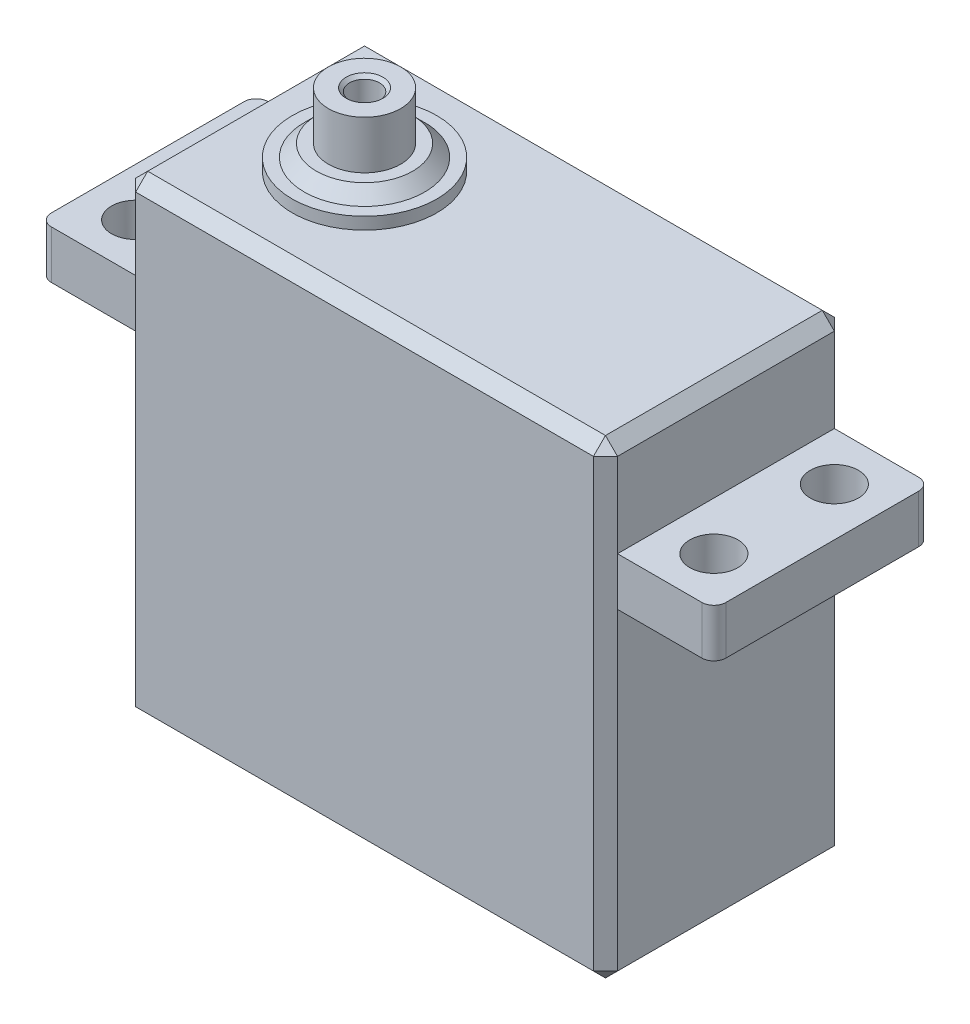
SolidWorks part; units mm, degrees
ref_plane "前视基准面" through (0, 0, 0) normal (0, 0, 1) x (1, 0, 0)
ref_plane "上视基准面" through (0, 0, 0) normal (0, 1, 0) x (1, 0, 0)
ref_plane "右视基准面" through (0, 0, 0) normal (1, 0, 0) x (0, 0, -1)
other "Configuration Table"
sketch "草图1" plane through (0, 0, 0) normal (0, 1, 0) x (1, 0, 0)
  line L1 (-20, -10) -> (20, -10)
  line L2 (-20, -10) -> (-20, 10)
  line L3 (-20, 10) -> (20, 10)
  line L4 (20, -10) -> (20, 10)
  line L5 (-20, -10) -> (20, 10) construction
  line L6 (-20, 10) -> (20, -10) construction
  point P0 (0, 0)
  dimension "D1" = 20
  dimension "D2" = 40
extrude "凸台-拉伸1" add sketch "草图1" along normal blind 39
chamfer "倒角1" distance 1 angle 45 12 edges at (20, 0, 0) (0, 0, -10) (-20, 0, 0) (0, 0, 10) (20, 39, 0) (20, 19.5, -10) (0, 39, -10) (20, 19.5, 10) (0, 39, 10) (-20, 19.5, 10) (-20, 39, 0) (-20, 19.5, -10)
sketch "草图12" plane through (-20, 0, 0) normal (-1, 0, 0) x (0, 0, 1)
  line L0 (9, 1) -> (9, 38) construction
  line L1 (-9, 27) -> (9, 27)
  line L2 (-9, 27) -> (-9, 31)
  line L3 (-9, 31) -> (9, 31)
  line L4 (9, 27) -> (9, 31)
  line L5 (-9, 27) -> (9, 31) construction
  line L6 (-9, 31) -> (9, 27) construction
  line L8 (9, 0) -> (-9, 0) construction
  line L9 (-9, 38) -> (-9, 1) construction
  point P0 (0, 29)
  dimension "D1" = 31
  dimension "D2" = 4
extrude "凸台-拉伸7" add sketch "草图12" along normal blind 8
mirror "镜向1" about plane through (0, 0, 0) normal (1, 0, 0) of "凸台-拉伸7"
sketch "草图13" plane through (0, 31, 0) normal (0, 1, 0) x (1, 0, 0)
  line L0 (-32.0979, 0) -> (34.7095, 0) construction
  line L1 (0, 14.3851) -> (0, -15.5224) construction
  circle A0 centre (-24, 5) radius 2
  circle A1 centre (-24, -5) radius 2
  circle A2 centre (24, -5) radius 2
  circle A3 centre (24, 5) radius 2
  dimension "D2" = 4
  dimension "D1" = 10
  dimension "D3" = 48
extrude "切除-拉伸2" cut sketch "草图13" against normal through all
fillet "圆角3" radius 1 4 edges at (28, 29, -9) (28, 29, 9) (-28, 29, 9) (-28, 29, -9)
sketch "草图14" plane through (0, 39, 0) normal (0, 1, 0) x (1, 0, 0)
  line L0 (-26.5797, 0) -> (3.9596, 0) construction
  circle A0 centre (-24, 5) radius 2 construction
  circle A1 centre (-24, 5) radius 2 construction
  circle A2 centre (-10, 0) radius 6
  dimension "D1" = 12
  dimension "D2" = 14
extrude "凸台-拉伸8" add sketch "草图14" along normal blind 1
sketch "草图15" plane through (0, 40, 0) normal (0, 1, 0) x (1, 0, 0)
  circle A0 centre (-10, 0) radius 5
  dimension "D1" = 10
extrude "凸台-拉伸9" add sketch "草图15" along normal blind 1
sketch "草图16" plane through (0, 41, 0) normal (0, 1, 0) x (1, 0, 0)
  circle A0 centre (-10, 0) radius 3
  dimension "D1" = 6
extrude "凸台-拉伸10" add sketch "草图16" along normal blind 4
sketch "草图17" plane through (0, 45, 0) normal (0, 1, 0) x (1, 0, 0)
  circle A0 centre (-10, 0) radius 1.5
  point P0 (-10, 0)
  dimension "D1" = 3
hole_wizard "M3 螺纹孔2" positions "草图17" profile "草图18" tap size "M3" standard "GB"
sketch "草图18" plane through (-10, 45, 0) normal (1, 0, 0) x (0, 0, 1)
  line L0 (0, 0) -> (0, 8.2511)
  line L1 (0, 8.2511) -> (1.25, 7.5)
  line L2 (1.25, 7.5) -> (1.25, 0.275)
  line L3 (1.25, 0.275) -> (1.525, 0)
  line L5 (1.525, 0) -> (0, 0)
  line L6 (-1.25, 0.275) -> (-1.525, 0) construction
  line L10 (0, 8.2511) -> (-1.25, 7.5) construction
  line L11 (0, -6.35) -> (0, 107.95) construction
  dimension "螺纹孔钻头直径" = 2.5
  dimension "螺纹孔钻头深度" = 7.5
  dimension "近端锥形沉头孔直径" = 3.05
  dimension "近端锥形沉头孔角度" = 90
  dimension "导头角度" = 118
cosmetic thread "孔螺纹线2" parameters "D1"=6, "D2"=3
chamfer "倒角3" distance 1 angle 45 1 edges at (-10, 41, 5)
